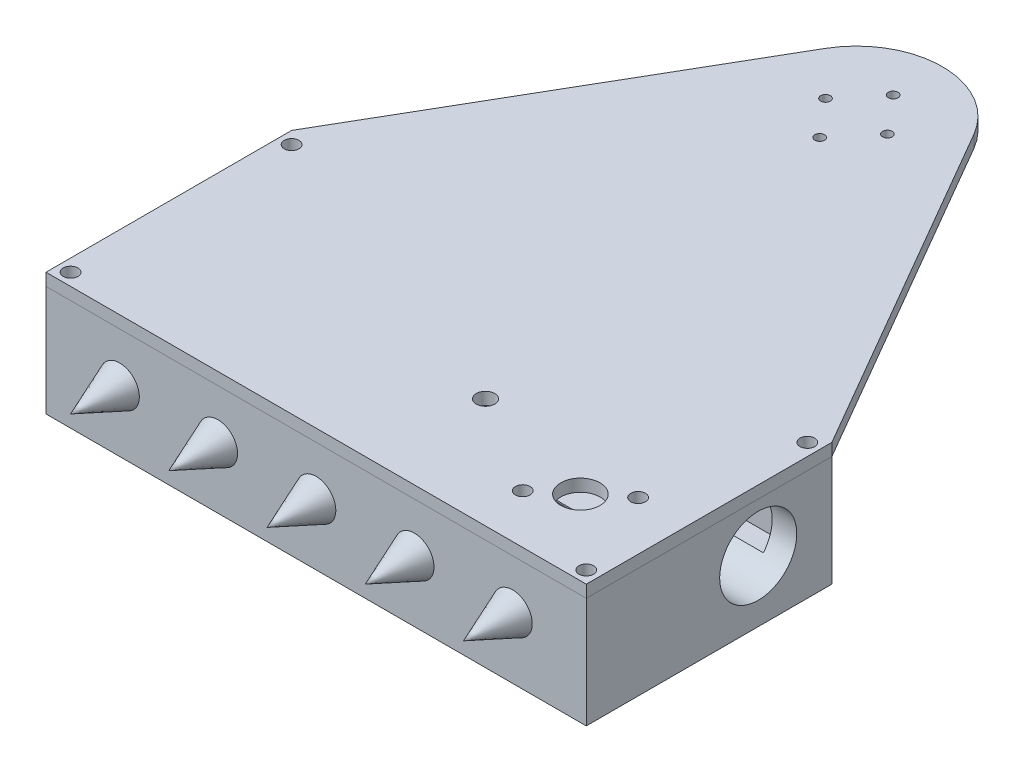
SolidWorks part; units mm, degrees
material "PLA/ABS"
ref_plane "Front Plane" through (0, 0, 0) normal (0, 0, 1) x (1, 0, 0)
ref_plane "Top Plane" through (0, 0, 0) normal (0, 1, 0) x (1, 0, 0)
ref_plane "Right Plane" through (0, 0, 0) normal (1, 0, 0) x (0, 0, -1)
other "Bounding Box"
ref_plane "Default Plane" through (-8.9266, -12.7485, 0) normal (-0.1736, 0.9848, 0) x (0.9848, 0.1736, 0)
sketch "Sketch1" plane through (0, 0, 0) normal (0, 1, 0) x (1, 0, 0)
  line L0 (0, 0) -> (0, -95.25) construction
  line L1 (0, -95.25) -> (-19.05, -95.25) construction
  line L2 (-76.2, -95.25) -> (-69.85, -95.25) construction
  line L3 (-69.85, -105.2195) -> (-19.05, -105.2195)
  line L4 (-69.85, -105.2195) -> (-69.85, -85.2805)
  line L5 (-69.85, -85.2805) -> (-19.05, -85.2805)
  line L6 (-19.05, -105.2195) -> (-19.05, -85.2805)
  line L7 (-69.85, -105.2195) -> (-19.05, -85.2805) construction
  line L8 (-69.85, -85.2805) -> (-19.05, -105.2195) construction
  line L9 (-88.9, -120.65) -> (-76.2, -120.65)
  line L10 (-88.9, -120.65) -> (-88.9, -69.85)
  line L11 (-88.9, -69.85) -> (-76.2, -69.85)
  line L12 (-76.2, -120.65) -> (-76.2, -69.85)
  line L13 (-88.9, -120.65) -> (-76.2, -69.85) construction
  line L14 (-88.9, -69.85) -> (-76.2, -120.65) construction
  line L15 (69.85, -85.2805) -> (19.05, -85.2805)
  line L16 (-63.5, -133.35) -> (-6.35, -133.35)
  line L17 (-63.5, -133.35) -> (-63.5, -116.84)
  line L18 (-63.5, -116.84) -> (-6.35, -116.84)
  line L19 (-6.35, -133.35) -> (-6.35, -116.84)
  line L20 (-63.5, -133.35) -> (-6.35, -116.84) construction
  line L21 (-63.5, -116.84) -> (-6.35, -133.35) construction
  line L22 (19.05, -105.2195) -> (19.05, -85.2805)
  line L23 (69.85, -105.2195) -> (19.05, -105.2195)
  line L24 (69.85, -105.2195) -> (69.85, -85.2805)
  line L25 (88.9, -69.85) -> (76.2, -69.85)
  line L26 (76.2, -120.65) -> (76.2, -69.85)
  line L27 (88.9, -120.65) -> (76.2, -120.65)
  line L28 (88.9, -120.65) -> (88.9, -69.85)
  line L30 (63.5, -133.35) -> (20.32, -133.35)
  line L31 (63.5, -133.35) -> (63.5, -113.2078)
  line L32 (63.5, -113.2078) -> (20.32, -113.2078)
  line L33 (20.32, -133.35) -> (20.32, -113.2078)
  line L34 (63.5, -133.35) -> (20.32, -113.2078) construction
  line L35 (63.5, -113.2078) -> (20.32, -133.35) construction
  line L36 (-69.85, -139.7) -> (69.85, -139.7)
  line L37 (-69.85, -139.7) -> (-69.85, -76.2)
  line L38 (-69.85, -76.2) -> (69.85, -76.2)
  line L39 (69.85, -139.7) -> (69.85, -76.2)
  line L40 (-69.85, -139.7) -> (69.85, -76.2) construction
  line L41 (-69.85, -76.2) -> (69.85, -139.7) construction
  circle A0 centre (0, 0) radius 69.85
  circle A1 centre (0, 0) radius 13.843
  point P3 (-34.925, -125.095)
  point P6 (-44.45, -95.25)
  point P12 (-82.55, -95.25)
  point P22 (0, -76.2)
  point P23 (0, -107.95)
  point P36 (0, -69.85)
  point P38 (41.91, -123.2789)
  dimension "D1" = 139.7
  dimension "D19" = 27.686
  dimension "D2" = 50.8
  dimension "D3" = 19.939
  dimension "D4" = 50.8
  dimension "D5" = 12.7
  dimension "D6" = 57.15
  dimension "D7" = 16.51
  dimension "D8" = 43.18
  dimension "D9" = 20.1422
  dimension "D10" = 6.35
  dimension "D11" = 139.7
  dimension "D12" = 44.45
  dimension "D13" = 6.35
  dimension "D14" = 6.35
  dimension "D15" = 6.35
  dimension "D16" = 6.35
  dimension "D17" = 63.5
  dimension "D18" = 6.35
sketch "Sketch2" plane through (0, 0, 0) normal (1, 0, 0) x (0, 0, -1)
  line L1 (-139.7, 12.7) -> (-76.2, 12.7)
  line L2 (-139.7, 12.7) -> (-139.7, -12.7)
  line L3 (-139.7, -12.7) -> (-76.2, -12.7)
  line L4 (-76.2, 12.7) -> (-76.2, -12.7)
  line L5 (-139.7, 12.7) -> (-76.2, -12.7) construction
  line L6 (-139.7, -12.7) -> (-76.2, 12.7) construction
  line L7 (-139.7, 12.7) -> (12.7, 12.7)
  line L8 (-139.7, 12.7) -> (-139.7, 15.875)
  line L9 (-139.7, 15.875) -> (12.7, 15.875)
  line L10 (12.7, 12.7) -> (12.7, 15.875)
  line L11 (-139.7, 12.7) -> (12.7, 15.875) construction
  line L12 (-139.7, 15.875) -> (12.7, 12.7) construction
  line L13 (-139.7, -12.7) -> (-76.2, -12.7)
  line L14 (-139.7, -12.7) -> (-139.7, -15.875)
  line L15 (-139.7, -15.875) -> (-76.2, -15.875)
  line L16 (-76.2, -12.7) -> (-76.2, -15.875)
  line L17 (-139.7, -12.7) -> (-76.2, -15.875) construction
  line L18 (-139.7, -15.875) -> (-76.2, -12.7) construction
  circle A0 centre (-95.25, 0) radius 25.4
  point P4 (-120.65, 0)
  point P5 (-107.95, 0)
  point P15 (-63.5, 14.2875)
  point P19 (-107.95, -14.2875)
  dimension "D1" = 25.4
  dimension "D2" = 3.175
  dimension "D3" = 12.7
sketch "Sketch3" plane through (0, 0, 0) normal (0, 1, 0) x (1, 0, 0)
  line L1 (-69.85, -139.7) -> (69.85, -139.7)
  line L2 (-69.85, -139.7) -> (-69.85, -76.2)
  line L3 (-69.85, -76.2) -> (69.85, -76.2)
  line L4 (69.85, -139.7) -> (69.85, -76.2)
  line L5 (-69.85, -139.7) -> (69.85, -76.2) construction
  line L6 (-69.85, -76.2) -> (69.85, -139.7) construction
  line L7 (-63.5, -82.55) -> (63.5, -82.55)
  line L8 (-63.5, -82.55) -> (-63.5, -133.35)
  line L9 (-63.5, -133.35) -> (63.5, -133.35)
  line L10 (63.5, -82.55) -> (63.5, -133.35)
  line L11 (-63.5, -82.55) -> (63.5, -133.35) construction
  line L12 (-63.5, -133.35) -> (63.5, -82.55) construction
  point P0 (0, -107.95)
  point P7 (0, -107.95)
extrude "Boss-Extrude1" add sketch "Sketch3" along normal up to vertex (12.7 mm away) and the other way up to vertex (12.7 mm away) up to point (0, 12.7, 139.7) other way up to point (0, -12.7, 139.7)
sketch "Sketch4" plane through (0, -12.7, 0) normal (0, -1, 0) x (1, 0, 0)
  line L1 (-69.85, 139.7) -> (69.85, 139.7)
  line L2 (-69.85, 139.7) -> (-69.85, 76.2)
  line L3 (-69.85, 76.2) -> (69.85, 76.2)
  line L4 (69.85, 139.7) -> (69.85, 76.2)
  line L5 (-69.85, 139.7) -> (69.85, 76.2) construction
  line L6 (-69.85, 76.2) -> (69.85, 139.7) construction
  point P0 (0, 107.95)
extrude "Boss-Extrude2" add sketch "Sketch4" along normal up to vertex (3.175 mm away) up to point (0, -15.875, 139.7)
sketch "Sketch5" plane through (0, 12.7, 0) normal (0, 1, 0) x (1, 0, 0)
  line L0 (-19.229, 11.1443) -> (-69.85, -76.2)
  line L1 (-69.85, -76.2) -> (-69.85, -139.7)
  line L2 (-69.85, -139.7) -> (69.85, -139.7)
  line L3 (69.85, -139.7) -> (69.85, -76.2)
  line L4 (69.85, -76.2) -> (19.229, 11.1443)
  arc A0 (-19.229, 11.1443) -> (19.229, 11.1443) centre (0, 0) cw
  dimension "D1" = 22.225
extrude "Boss-Extrude3" add sketch "Sketch5" along normal up to vertex (3.175 mm away) separate body up to point (0, 15.875, 139.7)
sketch "Sketch7" plane through (0, -12.7, 0) normal (0, 1, 0) x (1, 0, 0)
  line L0 (-19.05, -105.2195) -> (-19.05, -85.2805) construction
  line L1 (-63.5, -82.55) -> (-19.05, -82.55)
  line L2 (-63.5, -82.55) -> (-63.5, -107.95)
  line L3 (-63.5, -107.95) -> (-19.05, -107.95)
  line L4 (-19.05, -82.55) -> (-19.05, -107.95)
  line L5 (-63.5, -82.55) -> (-19.05, -107.95) construction
  line L6 (-63.5, -107.95) -> (-19.05, -82.55) construction
  line L7 (63.5, -82.55) -> (19.05, -82.55)
  line L8 (63.5, -82.55) -> (63.5, -107.95)
  line L9 (63.5, -107.95) -> (19.05, -107.95)
  line L10 (19.05, -82.55) -> (19.05, -107.95)
  line L11 (63.5, -82.55) -> (19.05, -107.95) construction
  line L12 (63.5, -107.95) -> (19.05, -82.55) construction
  line L13 (19.05, -105.2195) -> (19.05, -85.2805) construction
  line L14 (0, -95.25) -> (-19.05, -95.25) construction
  point P4 (-41.275, -95.25)
  point P10 (41.275, -95.25)
extrude "Boss-Extrude4" add sketch "Sketch7" along normal blind 6.35
sketch "Sketch6" plane through (-69.85, 0, 0) normal (-1, 0, 0) x (0, 0, 1)
  circle A0 centre (95.25, 0) radius 9.9695
extrude "Cut-Extrude1" cut sketch "Sketch6" against normal through all
ref_plane "Plane1" through (0, 0, 0) normal (1, 0, 0) x (0, 0, -1)
sketch "Sketch9" plane through (0, 0, 0) normal (1, 0, 0) x (0, 0, -1)
  line L0 (-139.7, 0) -> (-139.7, 5.08)
  line L1 (-139.7, 12.7) -> (-139.7, -15.875) construction
  line L2 (-139.7, 5.08) -> (-152.4, 0)
  line L3 (-152.4, 0) -> (-139.7, 0)
  dimension "D1" = 12.7
  dimension "D2" = 5.08
revolve "Revolve1" add sketch "Sketch9" angle 360 about L3
pattern_linear "LPattern1" count 3 spacing 25.4 along (-1, 0, 0) count 3 spacing 25.4 along (1, 0, 0) of "Revolve1"
sketch "Sketch13" plane through (0, -12.7, 0) normal (0, 1, 0) x (1, 0, 0)
  line L0 (-63.5, -107.95) -> (-19.05, -107.95) construction
  line L1 (-19.05, -82.55) -> (-48.26, -82.55)
  line L2 (-19.05, -82.55) -> (-19.05, -107.95)
  line L3 (-19.05, -107.95) -> (-48.26, -107.95)
  line L4 (-48.26, -82.55) -> (-48.26, -107.95)
  line L5 (-19.05, -82.55) -> (-48.26, -107.95) construction
  line L6 (-19.05, -107.95) -> (-48.26, -82.55) construction
  line L7 (-63.5, -82.55) -> (-63.5, -87.5644) construction
  line L9 (0, -17.4625) -> (0, 17.4625) construction
  line L10 (48.26, -82.55) -> (48.26, -107.95)
  line L11 (19.05, -107.95) -> (48.26, -107.95)
  line L12 (19.05, -82.55) -> (19.05, -107.95)
  line L13 (19.05, -82.55) -> (48.26, -82.55)
  point P4 (-33.655, -95.25)
  dimension "D1" = 15.24
extrude "Boss-Extrude5" add sketch "Sketch13" along normal blind 4.064
sketch "Sketch14" plane through (0, 0, 107.95) normal (0, 0, 1) x (1, 0, 0)
  line L0 (-48.26, -8.0762) -> (-48.26, -11.2291) construction
  line L1 (-43.18, -9.144) -> (-36.83, -9.144)
  line L2 (-43.18, -9.144) -> (-43.18, -11.684)
  line L3 (-43.18, -11.684) -> (-36.83, -11.684)
  line L4 (-36.83, -9.144) -> (-36.83, -11.684)
  line L5 (-43.18, -9.144) -> (-36.83, -11.684) construction
  line L6 (-43.18, -11.684) -> (-36.83, -9.144) construction
  line L7 (-48.26, -8.636) -> (-48.26, -9.9695) construction
  line L8 (-19.05, -6.35) -> (-63.5, -6.35) construction
  line L9 (-43.18, -5.08) -> (-36.83, -5.08)
  line L10 (-43.18, -5.08) -> (-43.18, -2.54)
  line L11 (-43.18, -2.54) -> (-36.83, -2.54)
  line L12 (-36.83, -5.08) -> (-36.83, -2.54)
  line L13 (-43.18, -5.08) -> (-36.83, -2.54) construction
  line L14 (-43.18, -2.54) -> (-36.83, -5.08) construction
  line L15 (-63.5, -12.7) -> (-19.05, -12.7) construction
  line L16 (0, -17.4625) -> (0, 17.4625) construction
  line L17 (43.18, -11.684) -> (36.83, -11.684)
  line L18 (36.83, -9.144) -> (36.83, -11.684)
  line L19 (43.18, -9.144) -> (36.83, -9.144)
  line L20 (43.18, -9.144) -> (43.18, -11.684)
  line L21 (43.18, -2.54) -> (36.83, -2.54)
  line L22 (36.83, -5.08) -> (36.83, -2.54)
  line L23 (43.18, -5.08) -> (36.83, -5.08)
  line L24 (43.18, -5.08) -> (43.18, -2.54)
  point P4 (-40.005, -10.414)
  point P13 (-40.005, -3.81)
  dimension "D1" = 2.54
  dimension "D2" = 6.35
  dimension "D3" = 5.08
  dimension "D4" = 1.27
  dimension "D5" = 1.016
extrude "Cut-Extrude2" cut sketch "Sketch14" against normal up to surface (31.75 mm away) up to face at (0, -1.5875, 76.2)
sketch "Sketch18" plane through (0, 0, 82.55) normal (0, 0, 1) x (1, 0, 0)
  line L0 (63.5, 12.7) -> (-63.5, 12.7) construction
  line L1 (-60.96, 12.7) -> (-50.8, 12.7)
  line L2 (-60.96, 12.7) -> (-60.96, 7.62)
  line L3 (-60.96, 7.62) -> (-50.8, 7.62)
  line L4 (-50.8, 12.7) -> (-50.8, 7.62)
  line L5 (-60.96, 12.7) -> (-50.8, 7.62) construction
  line L6 (-60.96, 7.62) -> (-50.8, 12.7) construction
  line L7 (-63.5, 12.7) -> (-63.5, -6.35) construction
  point P4 (-55.88, 10.16)
  dimension "D1" = 10.16
  dimension "D2" = 2.54
  dimension "D3" = 5.08
extrude "Cut-Extrude3" cut sketch "Sketch18" against normal up to surface (6.35 mm away) up to face at (-40.005, -3.81, 76.2)
sketch "Sketch19" plane through (0, 12.7, 0) normal (0, 1, 0) x (1, 0, 0)
  line L0 (-69.85, -76.2) -> (-69.85, -139.7) construction
  line L1 (-60.96, -76.2) -> (-69.85, -76.2) construction
  line L2 (-63.5, -82.55) -> (-63.5, -133.35) construction
  line L5 (69.85, -139.7) -> (69.85, -76.2) construction
  line L6 (69.85, -76.2) -> (-50.8, -76.2) construction
  line L7 (-69.85, -139.7) -> (69.85, -139.7) construction
  line L8 (-63.5, -133.35) -> (63.5, -133.35) construction
  circle A0 centre (-66.675, -79.375) radius 3.175 construction
  circle A1 centre (-66.675, -79.375) radius 0.635
  circle A2 centre (66.675, -79.375) radius 3.175 construction
  circle A3 centre (66.675, -79.375) radius 0.635
  circle A4 centre (-66.675, -136.525) radius 3.175 construction
  circle A5 centre (-66.675, -136.525) radius 0.635
  circle A6 centre (66.675, -136.525) radius 3.175 construction
  circle A7 centre (66.675, -136.525) radius 0.635
  point P12 (-67.1528, -107.95)
  point P13 (-66.675, -110.3234)
  point P17 (-7.4919, -155.8096)
  point P18 (66.1994, -130.9833)
  point P19 (0, 0)
  point P20 (66.7213, -131.1466)
  point P24 (73.8891, -98.2746)
  point P25 (64.7019, -81.7599)
  dimension "D1" = 1.27
  dimension "D2" = 6.35
extrude "Cut-Extrude4" cut sketch "Sketch19" against normal blind 25.4
sketch "Sketch20" plane through (0, 15.875, 0) normal (0, 1, 0) x (1, 0, 0)
  circle A0 centre (-66.675, -79.375) radius 1.905
  circle A1 centre (-66.675, -136.525) radius 1.905
  circle A2 centre (66.675, -136.525) radius 1.905
  circle A3 centre (66.675, -79.375) radius 1.905
  dimension "D1" = 3.81
  dimension "D2" = 3.81
  dimension "D3" = 3.81
  dimension "D4" = 3.81
extrude "Cut-Extrude7" cut sketch "Sketch20" against normal up to surface (3.175 mm away) up to face at (0, 12.7, 66.4051)
sketch "Sketch23" plane through (0, 15.875, 0) normal (0, 1, 0) x (1, 0, 0)
  line L0 (-69.85, -139.7) -> (69.85, -139.7) construction
  line L1 (57.15, -113.6085) -> (40.715, -113.6085) construction
  line L2 (57.15, -113.6085) -> (57.15, -127) construction
  line L3 (57.15, -127) -> (40.715, -127) construction
  line L4 (40.715, -113.6085) -> (40.715, -127) construction
  line L5 (57.15, -113.6085) -> (40.715, -127) construction
  line L6 (57.15, -127) -> (40.715, -113.6085) construction
  line L7 (69.85, -139.7) -> (69.85, -76.2) construction
  circle A0 centre (48.9325, -120.3043) radius 5.08
  circle A1 centre (57.15, -113.6085) radius 1.905
  circle A2 centre (40.715, -127) radius 1.905
  circle A4 centre (15.315, -111.2273) radius 2.3812
  point P0 (48.9325, -120.3043)
  point P17 (-1.6289, -105.4583)
  dimension "D1" = 10.16
  dimension "D2" = 3.81
  dimension "D3" = 10.6
  dimension "D4" = 12.7
  dimension "D7" = 4.7625
  dimension "D8" = 25.4
  dimension "D5" = 12.7
  dimension "D6" = 13.3915
extrude "Cut-Extrude8" cut sketch "Sketch23" against normal up to surface (3.175 mm away) up to face at (-66.675, 12.7, 77.47)
sketch "Sketch24" plane through (0, 15.875, 0) normal (0, 1, 0) x (1, 0, 0)
  circle A0 centre (0, 0) radius 8 construction
  circle A1 centre (0, 0) radius 9.5 construction
  circle A2 centre (0, 9.5) radius 1.25
  circle A3 centre (0, -9.5) radius 1.25
  circle A4 centre (-8, 0) radius 1.25
  circle A5 centre (8, 0) radius 1.25
  dimension "D1" = 19
  dimension "D2" = 16
  dimension "D3" = 2.5
  dimension "D4" = 2.5
  dimension "D5" = 2.5
  dimension "D6" = 2.5
extrude "Cut-Extrude9" cut sketch "Sketch24" against normal up to surface (3.175 mm away) up to face at (15.315, 12.7, 108.846)
